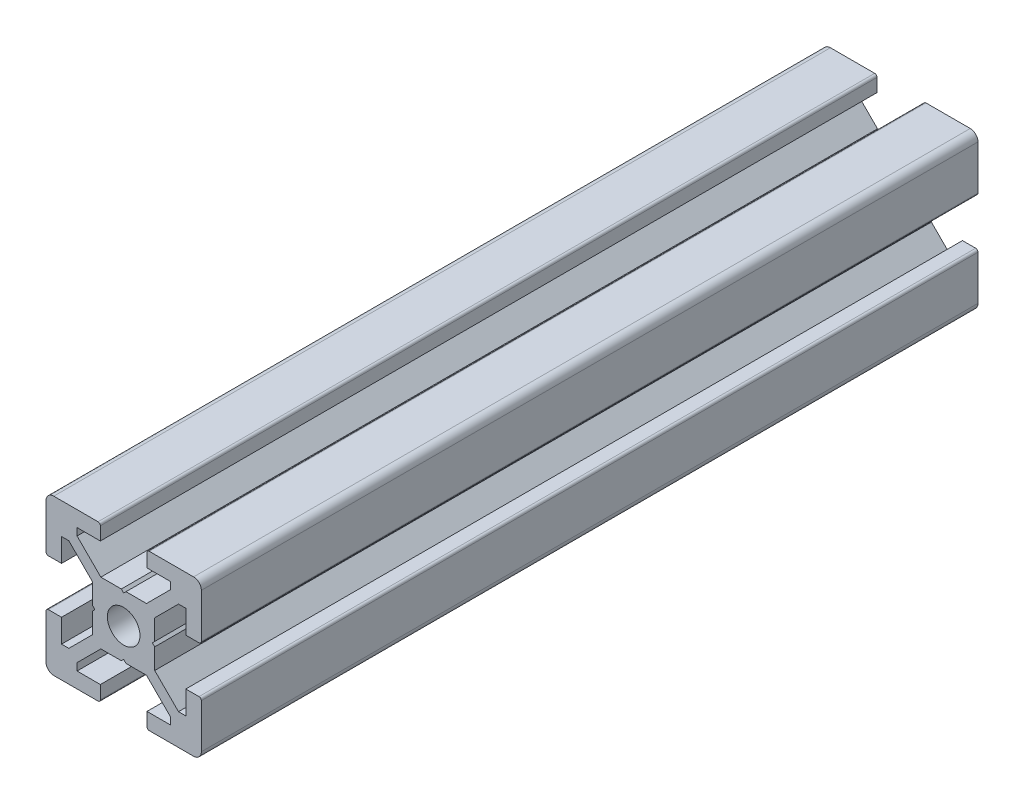
SolidWorks part; units mm, degrees
ref_plane "Front Plane" through (0, 0, 0) normal (0, 0, 1) x (1, 0, 0)
ref_plane "Top Plane" through (0, 0, 0) normal (0, 1, 0) x (1, 0, 0)
ref_plane "Right Plane" through (0, 0, 0) normal (1, 0, 0) x (0, 0, -1)
sketch "Sketch1" plane through (0, 0, 0) normal (0, 0, -1) x (-1, 0, 0)
  line L0 (10, 3.3) -> (10, 9)
  line L1 (9, 10) -> (3.3, 10)
  line L2 (3, 9.7) -> (3, 8)
  line L3 (3, 8) -> (6, 8)
  line L4 (6, 8) -> (6, 7.0607)
  line L5 (6, 7.0607) -> (2.9393, 4)
  line L6 (2.9393, 4) -> (0.3, 4)
  line L7 (0.3, 4) -> (0, 3.7)
  line L8 (0, 3.7) -> (-0.3, 4)
  line L9 (-0.3, 4) -> (-2.9393, 4)
  line L10 (-2.9393, 4) -> (-6, 7.0607)
  line L11 (-6, 7.0607) -> (-6, 8)
  line L12 (-6, 8) -> (-3, 8)
  line L13 (-3, 8) -> (-3, 9.7)
  line L14 (-3.3, 10) -> (-9, 10)
  line L15 (-10, 9) -> (-10, 3.3)
  line L16 (-9.7, 3) -> (-8, 3)
  line L17 (-8, 3) -> (-8, 6)
  line L18 (-8, 6) -> (-7.0607, 6)
  line L19 (-7.0607, 6) -> (-4, 2.9393)
  line L20 (-4, 2.9393) -> (-4, 0.3)
  line L21 (-4, 0.3) -> (-3.7, 0)
  line L22 (-3.7, 0) -> (-4, -0.3)
  line L23 (-4, -0.3) -> (-4, -2.9393)
  line L24 (-4, -2.9393) -> (-7.0607, -6)
  line L25 (-7.0607, -6) -> (-8, -6)
  line L26 (-8, -6) -> (-8, -3)
  line L27 (-8, -3) -> (-9.7, -3)
  line L28 (-10, -3.3) -> (-10, -9)
  line L29 (-9, -10) -> (-3.3, -10)
  line L30 (-3, -9.7) -> (-3, -8)
  line L31 (-3, -8) -> (-6, -8)
  line L32 (-6, -8) -> (-6, -7.0607)
  line L33 (-6, -7.0607) -> (-2.9393, -4)
  line L34 (-2.9393, -4) -> (-0.3, -4)
  line L35 (-0.3, -4) -> (0, -3.7)
  line L36 (0, -3.7) -> (0.3, -4)
  line L37 (0.3, -4) -> (2.9393, -4)
  line L38 (2.9393, -4) -> (6, -7.0607)
  line L39 (6, -7.0607) -> (6, -8)
  line L40 (6, -8) -> (3, -8)
  line L41 (3, -8) -> (3, -9.7)
  line L42 (3.3, -10) -> (9, -10)
  line L43 (10, -9) -> (10, -3.3)
  line L44 (9.7, -3) -> (8, -3)
  line L45 (8, -3) -> (8, -6)
  line L46 (8, -6) -> (7.0607, -6)
  line L47 (7.0607, -6) -> (4, -2.9393)
  line L48 (4, -2.9393) -> (4, -0.3)
  line L49 (4, -0.3) -> (3.7, 0)
  line L50 (3.7, 0) -> (4, 0.3)
  line L51 (4, 0.3) -> (4, 2.9393)
  line L52 (4, 2.9393) -> (7.0607, 6)
  line L53 (7.0607, 6) -> (8, 6)
  line L54 (8, 6) -> (8, 3)
  line L55 (8, 3) -> (9.7, 3)
  line L56 (9, -9) -> (-9, 9) construction
  line L57 (-9, -9) -> (9, 9) construction
  line L58 (-3.7, 0) -> (3.7, 0) construction
  line L59 (0, -3.7) -> (0, 3.7) construction
  circle A0 centre (0, 0) radius 2.1
  arc A1 (10, 9) -> (9, 10) centre (9, 9) ccw
  arc A2 (3.3, 10) -> (3, 9.7) centre (3.3, 9.7) ccw
  arc A3 (-3, 9.7) -> (-3.3, 10) centre (-3.3, 9.7) ccw
  arc A4 (-9, 10) -> (-10, 9) centre (-9, 9) ccw
  arc A5 (-10, 3.3) -> (-9.7, 3) centre (-9.7, 3.3) ccw
  arc A6 (-9.7, -3) -> (-10, -3.3) centre (-9.7, -3.3) ccw
  arc A7 (-10, -9) -> (-9, -10) centre (-9, -9) ccw
  arc A8 (-3.3, -10) -> (-3, -9.7) centre (-3.3, -9.7) ccw
  arc A9 (3, -9.7) -> (3.3, -10) centre (3.3, -9.7) ccw
  arc A10 (9, -10) -> (10, -9) centre (9, -9) ccw
  arc A11 (10, -3.3) -> (9.7, -3) centre (9.7, -3.3) ccw
  arc A12 (9.7, 3) -> (10, 3.3) centre (9.7, 3.3) ccw
  point P83 (0, 0)
  point P85 (0, 0)
  point P86 (0, 0)
  dimension "D1" = 1
  dimension "D4" = 0.3
  dimension "D10" = 4.2
  dimension "D2" = 20
  dimension "D3" = 6
  dimension "D5" = 3
  dimension "D6" = 1.7
  dimension "D7" = 0.9393
  dimension "D8" = 0.6
  dimension "D9" = 4
  dimension "D11" = 3.0607
  dimension "D12" = 3.0607
  dimension "D13" = 3.0607
  dimension "D14" = 5.7
  dimension "D15" = 5.7
  dimension "D16" = 0.9393
  dimension "D17" = 0.9393
  dimension "D18" = 3.0607
extrude "Boss-Extrude1" add sketch "Sketch1" against normal mid plane 100
ref_axis "Axis1" through (0, 0, 50) along (0, 0, -1)
